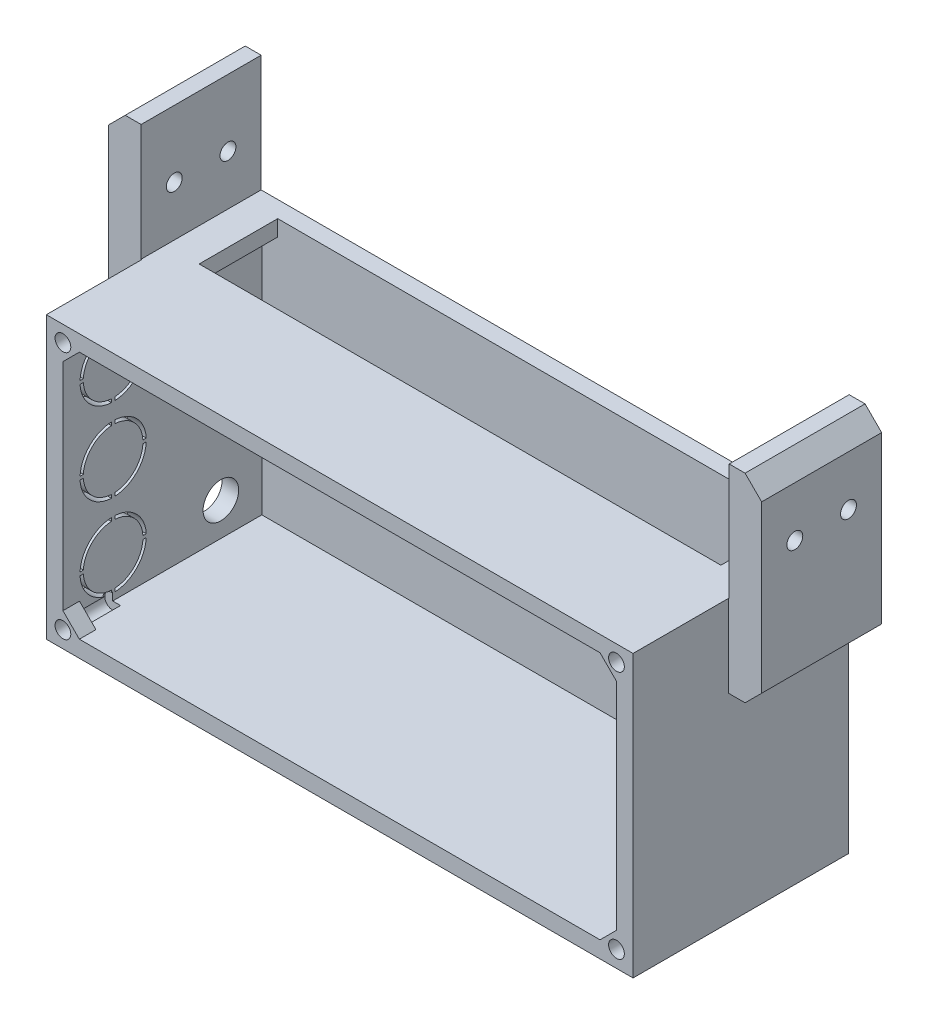
SolidWorks part; units mm, degrees
ref_plane "Front Plane" through (0, 0, 0) normal (0, 0, 1) x (1, 0, 0)
ref_plane "Top Plane" through (0, 0, 0) normal (0, 1, 0) x (1, 0, 0)
ref_plane "Right Plane" through (0, 0, 0) normal (1, 0, 0) x (0, 0, -1)
sketch "Sketch1" plane through (0, 0, 0) normal (0, 0, 1) x (1, 0, 0)
  line L1 (-88.5, -42.5) -> (88.5, -42.5)
  line L2 (-88.5, -42.5) -> (-88.5, 42.5)
  line L3 (-88.5, 42.5) -> (88.5, 42.5)
  line L4 (88.5, -42.5) -> (88.5, 42.5)
  line L5 (-88.5, -42.5) -> (88.5, 42.5) construction
  line L6 (-88.5, 42.5) -> (88.5, -42.5) construction
  point P0 (0, 0)
  dimension "D1" = 177
  dimension "D2" = 85
extrude "Boss-Extrude1" add sketch "Sketch1" along normal blind 65
shell "Shell1" thickness 5 removed face at (0, 0, 65)
sketch "Sketch2" plane through (0, 37.5, 0) normal (0, -1, 0) x (1, 0, 0)
  line L0 (78.7, 5) -> (-78.7, 5) construction
  line L1 (78.7, 28.7) -> (78.7, 5) construction
  line L2 (-78.7, 28.7) -> (78.7, 28.7) construction
  line L3 (-78.7, 5) -> (-78.7, 28.7) construction
  line L4 (78.7, 5) -> (-78.7, 5)
  line L5 (78.7, 28.7) -> (78.7, 5)
  line L6 (-78.7, 28.7) -> (78.7, 28.7)
  line L7 (-78.7, 5) -> (-78.7, 28.7)
extrude "Cut-Extrude1" cut sketch "Sketch2" against normal through all
ref_plane "Plane2" through (0, 0, 29.7) normal (0, 0, -1) x (-1, 0, 0)
sketch "Sketch3" plane through (0, 0, 29.7) normal (0, 0, -1) x (-1, 0, 0)
  line L1 (83.5, 37.5) -> (28.5, 37.5)
  line L2 (83.5, 37.5) -> (83.5, -39.3939)
  line L3 (83.5, -39.3939) -> (28.5, -39.3939)
  line L4 (28.5, 37.5) -> (28.5, -39.3939)
  line L8 (-83.5, 37.5) -> (-83.5, -37.5)
  line L9 (-78.7, 37.5) -> (-83.5, 37.5)
  line L10 (-78.7, 42.5) -> (-78.7, 37.5)
  line L11 (78.7, 42.5) -> (-78.7, 42.5)
  line L12 (78.7, 37.5) -> (78.7, 42.5)
  line L13 (83.5, 37.5) -> (78.7, 37.5)
  line L14 (83.5, -37.5) -> (83.5, 37.5)
  line L15 (-83.5, -37.5) -> (83.5, -37.5)
  line L16 (-83.5, 37.5) -> (-83.5, -37.5) construction
  line L17 (-78.7, 37.5) -> (-83.5, 37.5) construction
  line L18 (-78.7, 42.5) -> (-78.7, 37.5) construction
  line L19 (78.7, 42.5) -> (-78.7, 42.5) construction
  line L20 (78.7, 37.5) -> (78.7, 42.5) construction
  line L21 (83.5, 37.5) -> (78.7, 37.5) construction
  line L22 (83.5, -37.5) -> (83.5, 37.5) construction
  line L23 (-83.5, -37.5) -> (83.5, -37.5) construction
  dimension "D2" = 55
  dimension "D1" = 0
extrude "Boss-Extrude2" add sketch "Sketch3" against normal blind 5
sketch "Sketch4" plane through (-83.5, 0, 0) normal (1, 0, 0) x (0, 0, -1)
  line L0 (-17.35, 37.5) -> (-17.35, -27.5) construction
  line L4 (-5, 37.5) -> (-29.7, 37.5)
  line L5 (-29.7, 37.5) -> (-29.7, -37.5)
  line L6 (-29.7, -37.5) -> (-5, -37.5)
  line L7 (-5, -37.5) -> (-5, 37.5)
  line L8 (-5, 37.5) -> (-29.7, 37.5) construction
  line L9 (-29.7, 37.5) -> (-29.7, -37.5) construction
  line L10 (-29.7, -37.5) -> (-5, -37.5) construction
  line L11 (-5, -37.5) -> (-5, 37.5) construction
  circle A0 centre (-17.35, -27.5) radius 5.375
  dimension "D3" = 10.75
  dimension "D2" = 10
  dimension "D1" = 0
extrude "Cut-Extrude2" cut sketch "Sketch4" against normal through all
sketch "Sketch5" plane through (-83.5, 0, 0) normal (1, 0, 0) x (0, 0, -1)
  line L0 (-49.85, -37.5) -> (-49.85, 37.5) construction
  line L1 (-59.8375, -26) -> (-58.8361, -26)
  line L2 (-49.35, -35.4875) -> (-50.35, -35.4875)
  line L3 (-49.35, -35.4875) -> (-49.35, -34.4861)
  line L4 (-34.7, -37.5) -> (-34.7, 37.5)
  line L5 (-34.7, 37.5) -> (-65, 37.5)
  line L6 (-65, 37.5) -> (-65, -37.5)
  line L7 (-65, -37.5) -> (-34.7, -37.5)
  line L8 (-34.7, -37.5) -> (-34.7, 37.5) construction
  line L9 (-34.7, 37.5) -> (-65, 37.5) construction
  line L10 (-65, 37.5) -> (-65, -37.5) construction
  line L11 (-65, -37.5) -> (-34.7, -37.5) construction
  line L12 (-49.35, -34.4861) -> (-50.35, -34.4861)
  line L13 (-50.35, -35.4875) -> (-50.35, -34.4861)
  line L14 (-49.35, -35.4875) -> (-50.35, -34.4861) construction
  line L15 (-49.35, -34.4861) -> (-50.35, -35.4875) construction
  line L16 (-59.8375, -26) -> (-59.8375, -25)
  line L17 (-59.8375, -25) -> (-58.8361, -25)
  line L18 (-58.8361, -26) -> (-58.8361, -25)
  line L19 (-50.35, -15.5125) -> (-50.35, -16.5139)
  line L20 (-50.35, -15.5125) -> (-49.35, -15.5125)
  line L21 (-49.35, -15.5125) -> (-49.35, -16.5139)
  line L22 (-50.35, -16.5139) -> (-49.35, -16.5139)
  line L23 (-39.8625, -25) -> (-40.8639, -25)
  line L24 (-39.8625, -25) -> (-39.8625, -26)
  line L25 (-39.8625, -26) -> (-40.8639, -26)
  line L26 (-40.8639, -25) -> (-40.8639, -26)
  circle A0 centre (-49.85, -25.5) radius 10
  circle A1 centre (-49.85, -25.5) radius 9
  point P10 (-49.85, -34.9868)
  dimension "D2" = 20
  dimension "D3" = 12
  dimension "D5" = 1
  dimension "D1" = 0
  dimension "D4" = 1
  dimension "D6" = 4
extrude "Cut-Extrude3" cut sketch "Sketch5" against normal through all contours A1 L1 A0 L13 | A1 L3 A0 L25 | A1 L23 A0 L21 | A1 L19 A0 L17 region at (-83.5, -26.1342, 59.3368) region at (-83.5, -18.5238, 56.8262) region at (-83.5, -34.9868, 49.2158) region at (-83.5, -18.5238, 42.8738)
pattern_linear "LPattern2" count 3 spacing 25 along (0, 1, 0) of "Cut-Extrude3"
sketch "Sketch6" plane through (0, 0, 65) normal (0, 0, 1) x (1, 0, 0)
  line L0 (87.0093, 41.0093) -> (75.0278, 41.0093)
  line L1 (83.5, 37.5) -> (-83.5, 37.5) construction
  line L2 (75.0278, 41.0093) -> (87.0093, 29.0278)
  line L3 (83.5, -37.5) -> (83.5, 37.5) construction
  line L4 (87.0093, 29.0278) -> (87.0093, 41.0093)
  line L5 (87.0093, 41.0093) -> (81.0185, 35.0185) construction
  line L6 (83.5, 0) -> (-83.5, 0) construction
  line L7 (-83.5, 37.5) -> (-83.5, -37.5) construction
  line L8 (0, 37.5) -> (0, -37.5) construction
  line L9 (-83.5, -37.5) -> (83.5, -37.5) construction
  line L10 (75.0278, -41.0093) -> (87.0093, -29.0278)
  line L11 (87.0093, -41.0093) -> (75.0278, -41.0093)
  line L12 (87.0093, -29.0278) -> (87.0093, -41.0093)
  line L13 (-87.0093, -41.0093) -> (-75.0278, -41.0093)
  line L14 (-87.0093, -29.0278) -> (-87.0093, -41.0093)
  line L15 (-75.0278, -41.0093) -> (-87.0093, -29.0278)
  line L16 (-75.0278, 41.0093) -> (-87.0093, 29.0278)
  line L17 (-87.0093, 41.0093) -> (-75.0278, 41.0093)
  line L18 (-87.0093, 29.0278) -> (-87.0093, 41.0093)
  line L19 (88.5, 42.5) -> (-88.5, 42.5) construction
  line L21 (88.5, -42.5) -> (88.5, 42.5) construction
  circle A0 centre (83.5, 37.5) radius 2.375
  circle A1 centre (83.5, 37.5) radius 3.5093 construction
  circle A2 centre (83.5, -37.5) radius 2.375
  circle A3 centre (-83.5, -37.5) radius 2.375
  circle A4 centre (-83.5, 37.5) radius 2.375
  dimension "D2" = 4.75
  dimension "D1" = 11.9815
  dimension "D3" = 5
  dimension "D4" = 5
extrude "Boss-Extrude3" add sketch "Sketch6" against normal blind 5
sketch "Sketch7" plane through (0, 0, 65) normal (0, 0, 1) x (1, 0, 0)
  circle A0 centre (83.5, 37.5) radius 2.375
  arc A1 (81.125, 37.5) -> (83.5, 35.125) centre (83.5, 37.5) ccw construction
  circle A2 centre (83.5, -37.5) radius 2.375
  arc A3 (83.5, -35.125) -> (81.125, -37.5) centre (83.5, -37.5) ccw construction
  circle A4 centre (-83.5, -37.5) radius 2.375
  arc A5 (-81.125, -37.5) -> (-83.5, -35.125) centre (-83.5, -37.5) ccw construction
  circle A6 centre (-83.5, 37.5) radius 2.375
  arc A7 (-83.5, 35.125) -> (-81.125, 37.5) centre (-83.5, 37.5) ccw construction
extrude "Cut-Extrude4" cut sketch "Sketch7" against normal blind 15
sketch "Sketch8" plane through (0, 0, 0) normal (0, 0, -1) x (-1, 0, 0)
  line L0 (-88.5, -42.5) -> (-88.5, 42.5) construction
  line L1 (-88.5, 17.5) -> (-98.5, 17.5)
  line L2 (-88.5, 17.5) -> (-88.5, 77.5)
  line L3 (-88.5, 77.5) -> (-98.5, 77.5)
  line L4 (-98.5, 17.5) -> (-98.5, 77.5)
  line L5 (88.5, 42.5) -> (88.5, -42.5) construction
  line L6 (88.5, 17.5) -> (98.5, 17.5)
  line L7 (88.5, 17.5) -> (88.5, 77.5)
  line L8 (88.5, 77.5) -> (98.5, 77.5)
  line L9 (98.5, 17.5) -> (98.5, 77.5)
  line L10 (-88.5, 42.5) -> (88.5, 42.5) construction
  dimension "D1" = 10
  dimension "D2" = 60
  dimension "D3" = 25
extrude "Boss-Extrude4" add sketch "Sketch8" against normal blind 36.2
chamfer "Chamfer1" distance 5 angle 45 4 edges at (-98.5, 17.5, 18.1) (-98.5, 77.5, 18.1) (98.5, 77.5, 18.1) (98.5, 17.5, 18.1)
sketch "Sketch9" plane through (0, 0, 0) normal (0, 0, -1) x (-1, 0, 0)
  line L0 (-88.7, 42.3) -> (-88.7, 77.7)
  line L1 (-88.5, 42.5) -> (88.5, 42.5)
  line L2 (-88.5, 42.5) -> (-88.5, 77.5)
  line L3 (-88.5, 77.5) -> (88.5, 77.5)
  line L4 (88.5, 42.5) -> (88.5, 77.5)
  line L5 (-88.7, 77.7) -> (88.7, 77.7)
  line L6 (88.7, 42.3) -> (88.7, 77.7)
  line L7 (-88.7, 42.3) -> (88.7, 42.3)
  dimension "D1" = 0.2
extrude "Cut-Extrude5" cut sketch "Sketch9" against normal through all
sketch "Sketch10" plane through (-98.5, 0, 0) normal (1, 0, 0) x (0, 0, -1)
  line L0 (-36.2, 57.4) -> (-26.2, 57.4) construction
  line L1 (-36.2, 72.5) -> (0, 72.5) construction
  line L2 (-36.2, 72.5) -> (-36.2, 42.3) construction
  line L3 (-36.2, 42.3) -> (0, 42.3) construction
  line L4 (-36.2, 77.5) -> (-36.2, 72.5)
  line L5 (0, 77.5) -> (-36.2, 77.5)
  line L6 (0, 72.5) -> (0, 77.5)
  line L7 (-36.2, 72.5) -> (0, 72.5)
  line L8 (-36.2, 77.5) -> (-36.2, 72.5) construction
  line L9 (0, 77.5) -> (-36.2, 77.5) construction
  line L10 (0, 72.5) -> (0, 77.5) construction
  line L11 (-36.2, 72.5) -> (0, 72.5) construction
  line L12 (0, 72.5) -> (0, 42.3) construction
  line L13 (-26.2, 57.4) -> (-10, 57.4) construction
  line L14 (-10, 57.4) -> (0, 57.4) construction
  circle A0 centre (-26.2, 57.4) radius 2.4
  circle A1 centre (-10, 57.4) radius 2.4
  dimension "D2" = 4.8
  dimension "D3" = 10
  dimension "D1" = 0
extrude "Cut-Extrude6" cut sketch "Sketch10" along normal through all
sketch "Sketch11" plane through (0, 0, 34.7) normal (0, 0, 1) x (1, 0, 0)
  line L4 (-83.5, 37.5) -> (-83.5, -37.5)
  line L5 (-83.5, -37.5) -> (-28.5, -37.5)
  line L6 (-28.5, -37.5) -> (-28.5, 37.5)
  line L7 (-28.5, 37.5) -> (-83.5, 37.5)
  line L8 (-83.5, 37.5) -> (-83.5, -37.5)
  line L9 (-83.5, -37.5) -> (-28.5, -37.5)
  line L10 (-28.5, -37.5) -> (-28.5, 37.5)
  line L11 (-28.5, 37.5) -> (-83.5, 37.5)
  dimension "D1" = 0
extrude "Cut-Extrude7" cut sketch "Sketch11" against normal blind 5
sketch "Sketch12" plane through (0, 0, 0) normal (0, 0, -1) x (-1, 0, 0)
  circle A0 centre (11.2, -43.087) radius 1.5 construction
  circle A1 centre (-63.7, -43.087) radius 1.5 construction
  circle A2 centre (12.5, 5.213) radius 1.5 construction
  circle A3 centre (-69.6, 5.213) radius 1.5 construction
  circle A4 centre (11.2, -43.087) radius 1.5 construction
  circle A5 centre (-63.7, -43.087) radius 1.5 construction
  circle A6 centre (12.5, 5.213) radius 1.5 construction
  circle A7 centre (-69.6, 5.213) radius 1.5 construction
  circle A8 centre (-69.6, 5.213) radius 2.4
  circle A9 centre (12.5, 5.213) radius 2.4
  circle A10 centre (11.2, -43.087) radius 2.4
  circle A11 centre (-63.7, -43.087) radius 2.4
  dimension "D1" = 4.8
extrude "Cut-Extrude8" cut sketch "Sketch12" against normal up to surface (5 mm away)
